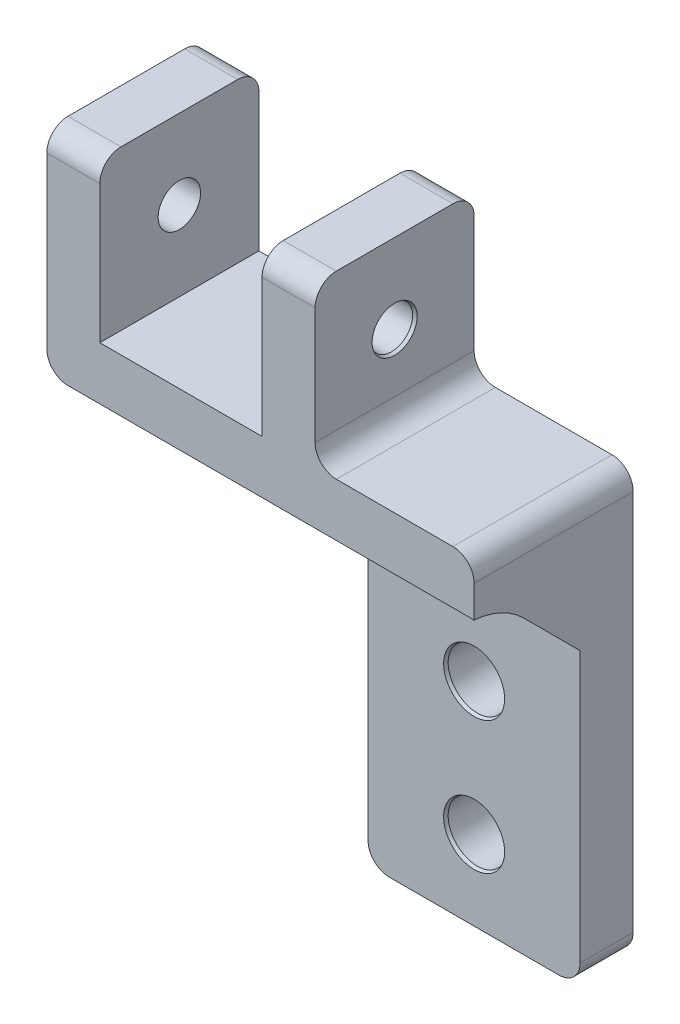
SolidWorks part; units mm, degrees
ref_plane "Front Plane" through (0, 0, 0) normal (0, 0, 1) x (1, 0, 0)
ref_plane "Top Plane" through (0, 0, 0) normal (0, 1, 0) x (1, 0, 0)
ref_plane "Right Plane" through (0, 0, 0) normal (1, 0, 0) x (0, 0, -1)
sketch "Sketch1" plane through (0, 0, 0) normal (1, 0, 0) x (0, 0, -1)
  line L0 (0, 20) -> (0, -20)
  line L1 (0, 20) -> (5, 20)
  line L2 (5, 20) -> (5, -20)
  line L3 (5, -20) -> (0, -20)
  line L4 (0, 20) -> (-10, 20)
  line L5 (-10, 20) -> (-10, 15)
  line L6 (-10, 15) -> (0, 15)
  point P4 (0, 0)
  dimension "D4" = 5
  dimension "D1" = 40
  dimension "D2" = 5
  dimension "D3" = 10
extrude "Boss-Extrude1" add sketch "Sketch1" along normal blind 20 contours L5 L6 L0 L4 | L3 L2 L1 L0 region at (0, 0, -2.5) region at (0, 17.5, 5)
sketch "Sketch3" plane through (0, 0, 0) normal (1, 0, 0) x (0, 0, -1)
  line L0 (-10, 20) -> (-10, 15)
  line L1 (-10, 15) -> (5, 15)
  line L2 (5, 20) -> (5, -20) construction
  line L3 (5, 15) -> (5, 20)
  line L4 (5, 20) -> (-10, 20)
extrude "Boss-Extrude2" add sketch "Sketch3" against normal blind 20.3
sketch "Sketch4" plane through (0, 20, 0) normal (0, 1, 0) x (1, 0, 0)
  line L2 (-15.3, 5) -> (0, 5)
  line L12 (-20.3, 5) -> (-15.3, 5)
  line L14 (20, 5) -> (-20.3, 5) construction
  line L17 (0, 0) -> (0, 5) construction
  line L19 (0, 5) -> (0, -10)
  line L21 (-15.3, 5) -> (-15.3, -10)
  line L22 (20, -10) -> (-20.3, -10) construction
  line L23 (-15.3, -10) -> (-20.3, -10)
  line L24 (-20.3, -10) -> (-20.3, 5)
  line L25 (0, -10) -> (5, -10)
  line L26 (5, -10) -> (5, 5)
  line L27 (5, 5) -> (0, 5)
  line M19 (20, 5) -> (-20.3, 5)
  line M20 (-20.3, 5) -> (-20.3, -10)
  line M21 (-20.3, -10) -> (20, -10)
  dimension "D1" = 5
chamfer "Chamfer2" distance 7.5 angle 45 1 edges at (10, 15, 0)
extrude "Boss-Extrude3" add sketch "Sketch4" along normal blind 15 contours L21 M19 M20 M21 | L26 L19 M21 M19 region at (-17.8, 20, 2.5) region at (2.5, 20, 2.5)
fillet "Fillet1" radius 7.5 2 edges at (10, 15, 7.5) (0, 15, 1.25)
sketch "Sketch5" plane through (0, 0, 0) normal (0, 0, 1) x (1, 0, 0)
  line L0 (10, 7.5) -> (10, 0) construction
  line L1 (20, 7.5) -> (0, 7.5) construction
  line L2 (10, -20) -> (10, -12.5) construction
  line L3 (20, -20) -> (0, -20) construction
  dimension "D1" = 7.5
hole_wizard "Ø5.5 (5.5) Diameter Hole1" positions "Sketch8" profile "Sketch9" hole size "Ø5.5" standard "ANSI Metric" end condition up to next
sketch "Sketch8" plane through (0, 0, 0) normal (0, 0, 1) x (1, 0, 0)
  point P0 (10, 0)
  point P3 (10, -12.5)
sketch "Sketch9" plane through (10, 0, 0) normal (1, 0, 0) x (0, -1, 0)
  line L0 (0, 0) -> (0, 5)
  line L1 (0, 5) -> (2.75, 5)
  line L2 (2.75, 5) -> (2.75, 0.3018)
  line L3 (2.75, 0.3018) -> (2.875, 0)
  line L5 (2.875, 0) -> (0, 0)
  line L6 (-2.75, 0.3018) -> (-2.875, 0) construction
  line L11 (0, -6.35) -> (0, 107.95) construction
  dimension "Thru Hole Dia." = 5.5
  dimension "Thru Hole Depth" = 5
  dimension "Near C'Sink Dia." = 5.75
  dimension "Near C'Sink Angle" = 45
ref_plane "Plane2" through (-7.65, 0, 0) normal (1, 0, 0) x (0, 0, -1)
sketch "Sketch11" plane through (-20.3, 0, 0) normal (-1, 0, 0) x (0, 0, 1)
  line L0 (2.5, 35) -> (2.5, 27.5) construction
  line L1 (-5, 35) -> (10, 35) construction
  point P1 (2.5, 27.5)
  dimension "D1" = 7.5
hole_wizard "Ø4.0 (4) Diameter Hole1" positions "Sketch11" profile "Sketch12" hole size "Ø4.0" standard "ANSI Metric" end condition up to next
sketch "Sketch12" plane through (-20.3, 27.5, 2.5) normal (0, 1, 0) x (0, 0, 1)
  line L0 (0, 0) -> (0, 5)
  line L1 (0, 5) -> (2, 5)
  line L2 (2, 5) -> (2, 0.3018)
  line L3 (2, 0.3018) -> (2.125, 0)
  line L5 (2.125, 0) -> (0, 0)
  line L6 (-2, 0.3018) -> (-2.125, 0) construction
  line L11 (0, -6.35) -> (0, 107.95) construction
  dimension "Thru Hole Dia." = 4
  dimension "Thru Hole Depth" = 5
  dimension "Near C'Sink Dia." = 4.25
  dimension "Near C'Sink Angle" = 45
mirror "Mirror1" about plane through (-7.65, 0, 0) normal (1, 0, 0) of "Ø4.0 (4) Diameter Hole1"
fillet "Fillet2" radius 2 9 edges at (5, 20, 2.5) (20, 20, 2.5) (-20.3, 15, 2.5) (0, -20, -2.5) (20, -20, -2.5) (-17.8, 35, -5) (-17.8, 35, 10) (2.5, 35, -5) (2.5, 35, 10)
